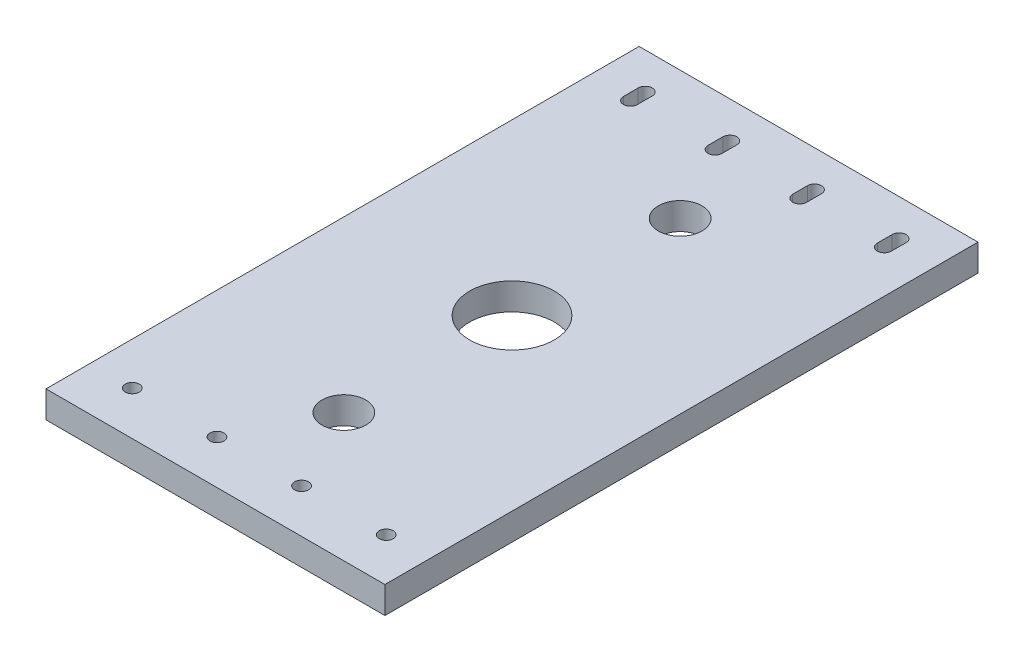
SolidWorks part; units mm, degrees
ref_plane "Front Plane" through (0, 0, 0) normal (0, 0, 1) x (1, 0, 0)
ref_plane "Top Plane" through (0, 0, 0) normal (0, 1, 0) x (1, 0, 0)
ref_plane "Right Plane" through (0, 0, 0) normal (1, 0, 0) x (0, 0, -1)
sketch "Sketch1" plane through (0, 0, 0) normal (0, 1, 0) x (1, 0, 0)
  line L1 (0, 0) -> (80, 0)
  line L2 (0, 0) -> (0, 140)
  line L3 (0, 140) -> (80, 140)
  line L4 (80, 0) -> (80, 140)
  dimension "D1" = 140
  dimension "D2" = 80
extrude "Boss-Extrude1" add sketch "Sketch1" along normal blind 6.35
sketch "Sketch2" plane through (0, 6.35, 0) normal (0, 1, 0) x (1, 0, 0)
  line L0 (0, 70) -> (80, 70) construction
  line L1 (0, 140) -> (0, 0) construction
  line L2 (80, 0) -> (80, 140) construction
  line L3 (40, 140) -> (40, 0) construction
  line L4 (80, 140) -> (0, 140) construction
  line L5 (0, 0) -> (80, 0) construction
  line L6 (0, 10.335) -> (80, 10.335) construction
  line L7 (0, 129.665) -> (80, 129.665) construction
  line L8 (30.01, 127.915) -> (30.01, 131.415) construction
  line L9 (28.36, 127.915) -> (28.36, 131.415)
  line L10 (31.66, 127.915) -> (31.66, 131.415)
  line L11 (10.03, 127.915) -> (10.03, 131.415) construction
  line L12 (8.38, 127.915) -> (8.38, 131.415)
  line L13 (11.68, 127.915) -> (11.68, 131.415)
  line L14 (49.99, 127.915) -> (49.99, 131.415) construction
  line L15 (51.64, 127.915) -> (51.64, 131.415)
  line L16 (48.34, 127.915) -> (48.34, 131.415)
  line L17 (69.97, 127.915) -> (69.97, 131.415) construction
  line L18 (71.62, 127.915) -> (71.62, 131.415)
  line L19 (68.32, 127.915) -> (68.32, 131.415)
  circle A0 centre (10.03, 10.335) radius 1.65
  circle A1 centre (30.01, 10.335) radius 1.65
  circle A2 centre (49.99, 10.335) radius 1.65
  circle A3 centre (69.97, 10.335) radius 1.65
  arc A4 (28.36, 127.915) -> (31.66, 127.915) centre (30.01, 127.915) ccw
  arc A5 (31.66, 131.415) -> (28.36, 131.415) centre (30.01, 131.415) ccw
  arc A6 (8.38, 127.915) -> (11.68, 127.915) centre (10.03, 127.915) ccw
  arc A7 (11.68, 131.415) -> (8.38, 131.415) centre (10.03, 131.415) ccw
  arc A8 (51.64, 127.915) -> (48.34, 127.915) centre (49.99, 127.915) cw
  arc A9 (48.34, 131.415) -> (51.64, 131.415) centre (49.99, 131.415) cw
  arc A10 (71.62, 127.915) -> (68.32, 127.915) centre (69.97, 127.915) cw
  arc A11 (68.32, 131.415) -> (71.62, 131.415) centre (69.97, 131.415) cw
  circle A12 centre (40, 70) radius 10
  circle A13 centre (40, 109.6875) radius 5.1594
  circle A14 centre (40, 30.3125) radius 5.1594
  point P26 (30.01, 129.665)
  point P33 (10.03, 129.665)
  point P40 (49.99, 129.665)
  point P47 (69.97, 129.665)
  dimension "D5" = 3.3
  dimension "D10" = 20
  dimension "D12" = 10.3187
  dimension "D1" = 59.665
  dimension "D2" = 59.665
  dimension "D3" = 9.99
  dimension "D4" = 19.98
  dimension "D6" = 3.3
  dimension "D7" = 3.5
  dimension "D8" = 9.99
  dimension "D9" = 19.98
  dimension "D11" = 39.6875
extrude "Cut-Extrude1" cut sketch "Sketch2" against normal through all
